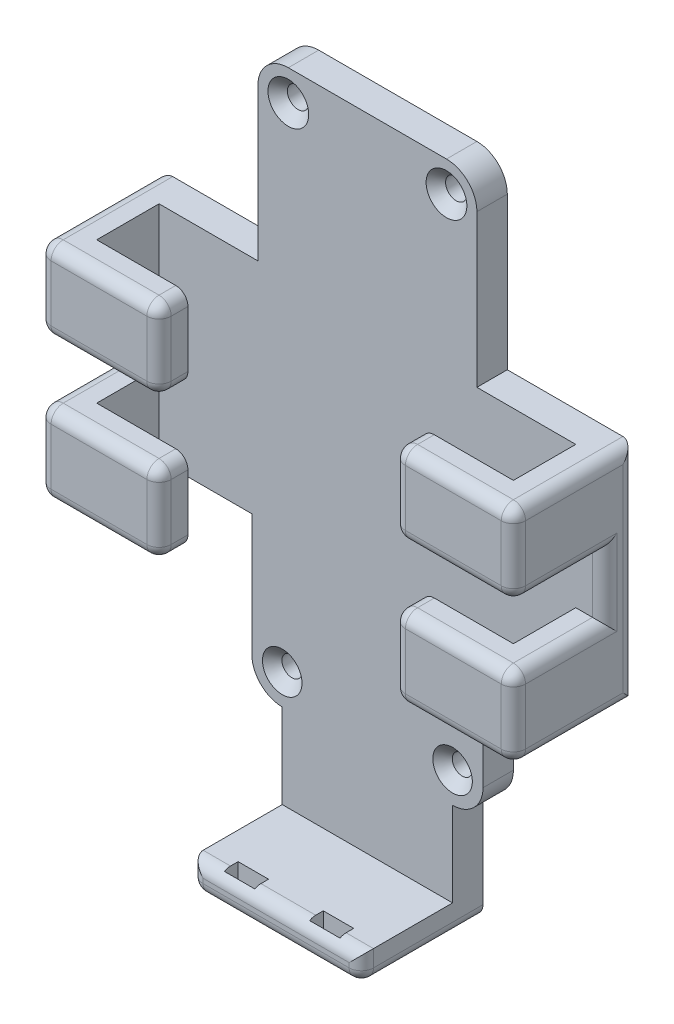
SolidWorks part; units mm, degrees
material "PLA Black"
ref_plane "Front Plane" through (0, 0, 0) normal (0, 0, 1) x (1, 0, 0)
ref_plane "Top Plane" through (0, 0, 0) normal (0, 1, 0) x (1, 0, 0)
ref_plane "Right Plane" through (0, 0, 0) normal (1, 0, 0) x (0, 0, -1)
sketch "Sketch1" plane through (0, 0, 0) normal (0, 0, 1) x (1, 0, 0)
  line L0 (-18, 16.2768) -> (76.3492, 16.2768) construction
  line L9 (0, 0) -> (0, 16.2768) construction
  line L22 (-18, 57.0268) -> (-18, -24.4732)
  line L23 (18, 57.0268) -> (18, 52.0268)
  line L32 (39, 32.0268) -> (39, -4.4732)
  line L40 (39, 32.0268) -> (18, 32.0268)
  line L41 (18, 52.0268) -> (18, 32.0268)
  line L44 (39, -4.4732) -> (19, -4.4732)
  line L45 (19, -24.4732) -> (19, -4.4732)
  line L46 (-13, 62.0268) -> (13, 62.0268)
  line L48 (-14, -29.3722) -> (-14, -48.1222)
  line L49 (-14, -48.1222) -> (14, -48.1222)
  line L50 (14, -48.1222) -> (14, -29.4732)
  circle A8 centre (-14, -24.4732) radius 1.65
  circle A9 centre (14, -24.4732) radius 1.65
  circle A17 centre (-13, 57.0268) radius 1.75
  circle A18 centre (13, 57.0268) radius 1.75
  arc A19 (13, 62.0268) -> (18, 57.0268) centre (13, 57.0268) cw
  arc A20 (-13, 62.0268) -> (-18, 57.0268) centre (-13, 57.0268) ccw
  arc A21 (-18, -24.4732) -> (-14, -29.3722) centre (-13, -24.4732) ccw
  arc A22 (19, -24.4732) -> (14, -29.4732) centre (14, -24.4732) cw
  point P21 (18, 62.0268)
  point P38 (0, 0)
  dimension "D5" = 40.75
  dimension "D6" = 26
  dimension "D7" = 5
  dimension "D8" = 4.899
  dimension "D9" = 3.3
  dimension "D10" = 3.3
  dimension "D13" = 13
  dimension "D16" = 5
  dimension "D17" = 3.5
  dimension "D12" = 5
  dimension "D15" = 40.75
  dimension "D2" = 3.5
  dimension "D1" = 28
  dimension "D3" = 14
  dimension "D11" = 5
  dimension "D14" = 16.2768
  dimension "D18" = 21
  dimension "D20" = 5
  dimension "D21" = 39
  dimension "D22" = 15.75
  dimension "D23" = 20.75
  dimension "D24" = 20
  dimension "18.75" = 18.75
extrude "Boss-Extrude1" add sketch "Sketch1" along normal blind 5
sketch "Sketch2" plane through (0, 0, 5) normal (0, 0, 1) x (1, 0, 0)
chamfer "Chamfer1" distance 1.6 angle 45 4 edges at (-12.35, -24.4732, 0) (15.65, -24.4732, 0) (11.25, 57.0268, 0) (-11.25, 57.0268, 0)
sketch "Sketch4" plane through (0, 0, 5) normal (0, 0, 1) x (1, 0, 0)
  line L5 (14, -48.1222) -> (14, -29.4732) construction
  line L15 (-14, -48.1222) -> (14, -48.1222)
  line L16 (-14, -48.1222) -> (-14, -43.3722)
  line L17 (-14, -43.3722) -> (14, -43.3722)
  line L18 (14, -48.1222) -> (14, -43.3722)
  dimension "D1" = 4.75
extrude "Boss-Extrude2" add sketch "Sketch4" along normal blind 15
sketch "Sketch7" plane through (0, 0, 5) normal (0, 0, 1) x (1, 0, 0)
  line L2 (39, 32.0268) -> (39, -4.4732)
  line L4 (34.25, 32.0268) -> (34.25, -4.4732)
  line L6 (34.25, 32.0268) -> (39, 32.0268)
  line L9 (34.25, -4.4732) -> (39, -4.4732)
  line L10 (19, -4.4732) -> (39, -4.4732) construction
  line L11 (39, 32.0268) -> (18, 32.0268) construction
  line L12 (39, -4.4732) -> (39, 32.0268) construction
  dimension "D1" = 4.75
extrude "Boss-Extrude3" add sketch "Sketch7" along normal blind 15
sketch "Sketch8" plane through (34.25, 0, 0) normal (-1, 0, 0) x (0, 0, 1)
  line L0 (20, 32.0268) -> (20, -4.4732) construction
  line L5 (5, 32.0268) -> (5, -4.4732) construction
  line L7 (20, 13.7768) -> (70.3215, 13.7768) construction
  line L13 (20, 8.7768) -> (5, 8.7768)
  line L14 (20, 8.7768) -> (20, 18.7768)
  line L15 (20, 18.7768) -> (5, 18.7768)
  line L16 (5, 8.7768) -> (5, 18.7768)
  dimension "D3" = 10
  dimension "D4" = 5
extrude "Cut-Extrude1" cut sketch "Sketch8" against normal blind 10
sketch "Sketch9" plane through (34.25, 0, 0) normal (-1, 0, 0) x (0, 0, 1)
  line L0 (20, 18.7768) -> (5, 18.7768) construction
  line L1 (20, 32.0268) -> (15.25, 32.0268)
  line L2 (20, 32.0268) -> (20, 18.7768)
  line L3 (20, 18.7768) -> (15.25, 18.7768)
  line L4 (15.25, 32.0268) -> (15.25, 18.7768)
  line L6 (20, 8.7768) -> (15.25, 8.7768)
  line L7 (20, 8.7768) -> (20, -4.4732)
  line L8 (20, -4.4732) -> (15.25, -4.4732)
  line L9 (15.25, 8.7768) -> (15.25, -4.4732)
  line L10 (20, 32.0268) -> (5, 32.0268) construction
  line L11 (20, -4.4732) -> (5, -4.4732) construction
  line L12 (20, 32.0268) -> (20, 18.7768) construction
  dimension "D1" = 4.75
  dimension "D2" = 4.75
extrude "Boss-Extrude4" add sketch "Sketch9" along normal blind 15
ref_plane "Plane1" through (0, 0, 0) normal (1, 0, 0) x (0, 0, -1)
mirror "Mirror1" about plane through (0, 0, 0) normal (1, 0, 0) of "Boss-Extrude3", "Boss-Extrude1", "Boss-Extrude4"
sketch "Sketch10" plane through (0, -43.3722, 0) normal (0, 1, 0) x (1, 0, 0)
  line L0 (-14, -15) -> (14, -15) construction
  line L1 (-14, -20) -> (-14, -5) construction
  line L2 (14, -20) -> (14, -5) construction
  line L4 (-14, -17.5) -> (14, -17.5) construction
  line L5 (-9.5, -16.75) -> (-4.5, -16.75)
  line L6 (-9.5, -16.75) -> (-9.5, -19)
  line L7 (-9.5, -19) -> (-4.5, -19)
  line L8 (-4.5, -16.75) -> (-4.5, -19)
  line L13 (14, -20) -> (-14, -20) construction
  line L14 (0, -10.3125) -> (0, 10.3125) construction
  line L15 (9.5, -19) -> (4.5, -19)
  line L16 (4.5, -16.75) -> (4.5, -19)
  line L17 (9.5, -16.75) -> (4.5, -16.75)
  line L18 (9.5, -16.75) -> (9.5, -19)
  dimension "D1" = 5
  dimension "D2" = 2.5
  dimension "D3" = 1.5
  dimension "D4" = 1.5
  dimension "D5" = 5
  dimension "D6" = 4.5
extrude "Cut-Extrude2" cut sketch "Sketch10" against normal blind 15
sketch "Sketch11" plane through (-34.25, 0, 0) normal (1, 0, 0) x (0, 0, -1)
  line L1 (-20, 18.7768) -> (-5, 18.7768)
  line L2 (-20, 18.7768) -> (-20, 8.7768)
  line L3 (-20, 8.7768) -> (-5, 8.7768)
  line L4 (-5, 18.7768) -> (-5, 8.7768)
extrude "Cut-Extrude3" cut sketch "Sketch11" against normal blind 15
fillet "Fillet1" radius 2 46 edges at (39, 25.4018, 20) (29.125, 18.7768, 20) (29.125, 8.7768, 20) (39, 13.7768, 5) (39, 8.7768, 12.5) (39, 18.7768, 12.5) (19.25, 25.4018, 20) (19.25, 32.0268, 17.625) (19.25, 18.7768, 17.625) (19.25, 2.1518, 20) (19.25, 8.7768, 17.625) (19.25, -4.4732, 17.625) (-39, 32.0268, 10) (-39, -4.4732, 10) (39, 13.7768, 0) (-39, 13.7768, 0) (-29.125, -4.4732, 20) (-29.125, 32.0268, 20) (-39, 2.1518, 20) (-19.25, 25.4018, 20) (-19.25, 18.7768, 17.625) (-29.125, 18.7768, 20) (-19.25, 32.0268, 17.625) (-19.25, 2.1518, 20) (-29.125, 8.7768, 20) (-19.25, -4.4732, 17.625) (-19.25, 8.7768, 17.625) (39, 32.0268, 10) (-7, -48.1222, 19) (39, -4.4732, 10) (-7, -43.3722, 19) (14, -48.1222, 10) (-14, -48.1222, 10) (7, -48.1222, 19) (7, -43.3722, 19) (-39, 25.4018, 20) (-39, 13.7768, 5) (-39, 18.7768, 12.5) (-39, 8.7768, 12.5) (-14, -45.7472, 20) (0, -48.1222, 20) (14, -45.7472, 20) (0, -43.3722, 20) (29.125, -4.4732, 20) (39, 2.1518, 20) (29.125, 32.0268, 20)
chamfer "Chamfer2" distance 1.6 angle 45 4 edges at (-12.35, -24.4732, 5) (-11.25, 57.0268, 5) (11.25, 57.0268, 5) (15.65, -24.4732, 5)
